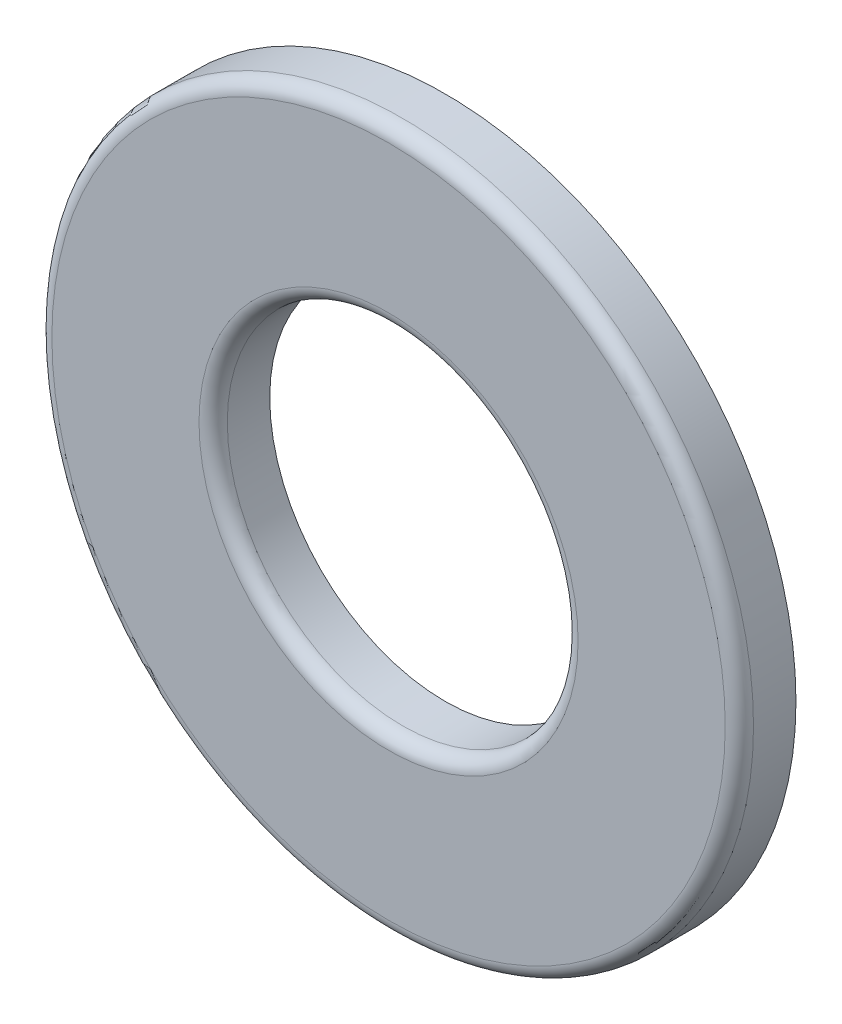
SolidWorks part; units mm, degrees
note: '?' marks a value the reader was unsure of.
other "Imported1" parameters "D1"=0.4159, "TH"=1.0287, "Thickness"=1.6637
ref_plane "Front Plane" through (0, 0, 0) normal (0, 0, 1) x (1, 0, 0)
ref_plane "Top Plane" through (0, 0, 0) normal (0, 1, 0) x (1, 0, 0)
ref_plane "Right Plane" through (0, 0, 0) normal (1, 0, 0) x (0, 0, -1)
sketch "Sketch1" plane through (0, 0, 0) normal (0, 0, 1) x (1, 0, 0)
  line L0 (-10.3124, 0) -> (10.3124, 0) construction
  line L1 (-5.1562, 0) -> (5.1562, 0) construction
  circle A0 centre (0, 0) radius 5.1562 construction
  circle A1 centre (0, 0) radius 10.3124 construction
  point P8 (0, 0)
  point P9 (0, 10.3124)
  point P11 (5.1562, 0)
  dimension "ID" = 10.3124
  dimension "OD" = 20.6248
sketch "Sketch2" plane through (0, 0, 0) normal (1, 0, 0) x (0, 0, -1)
  line L0 (-0.8318, 10.3124) -> (0.8319, 10.3124) construction
  point P2 (0, 10.3124)
sketch "Sketch3" plane through (0, 0, 0) normal (0, 0, 1) x (1, 0, 0)
  circle A0 centre (0, 0) radius 5.1562
  circle A1 centre (0, 0) radius 10.3124
extrude "Boss-Extrude1" add sketch "Sketch3" along normal up to vertex (0.8318 mm away) and the other way up to vertex (0.8318 mm away) up to point (0, 10.3124, 0.8318) other way up to point (0, 10.3124, -0.8319)
fillet "Fillet1" radius 0.4159 2 edges at (10.3124, 0, 0.8318) (5.1562, 0, 0.8318)
ref_axis "Center Axis 1" through (0, 0, 0.4159) along (0, 0, -1)?
equation "\"D1@Fillet1\"=\"Thickness@Sketch2\"/4"
